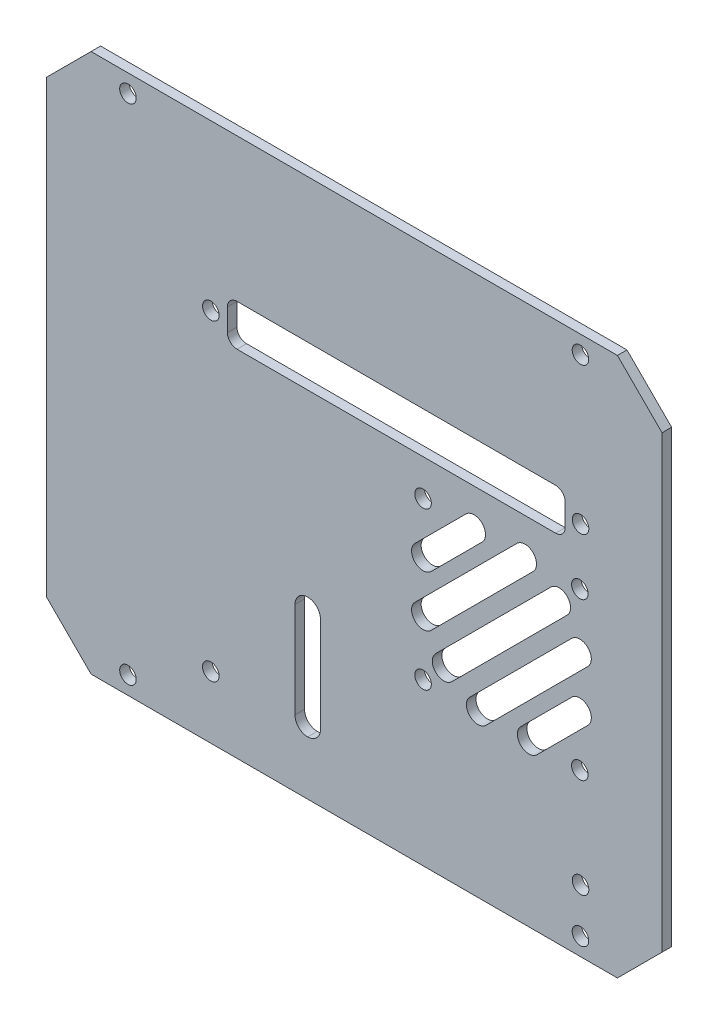
SolidWorks part; units mm, degrees
ref_plane "前视基准面" through (0, 0, 0) normal (0, 0, 1) x (1, 0, 0)
ref_plane "上视基准面" through (0, 0, 0) normal (0, 1, 0) x (1, 0, 0)
ref_plane "右视基准面" through (0, 0, 0) normal (1, 0, 0) x (0, 0, -1)
sketch "草图2" plane through (0, 0, -39.19) normal (0, 0, -1) x (-1, 0, 0)
  line L32 (-47.3467, -34.0538) -> (-40.3426, -41.058)
  line L33 (-40.3426, -41.058) -> (42.2491, -41.058)
  line L34 (42.2491, -41.058) -> (49.2533, -34.0538)
  line L35 (49.2533, -34.0538) -> (49.2533, 36.5378)
  line L36 (49.2533, 36.5378) -> (42.2491, 43.542)
  line L37 (-47.3467, 36.5378) -> (-47.3467, -34.0538)
  line L38 (-40.3426, 43.542) -> (-47.3467, 36.5378)
  line L39 (42.2491, 43.542) -> (-40.3426, 43.542)
  line L40 (-47.3467, -34.0538) -> (-40.3426, -41.058)
  line L41 (-40.3426, -41.058) -> (42.2491, -41.058)
  line L42 (42.2491, -41.058) -> (49.2533, -34.0538)
  line L43 (49.2533, -34.0538) -> (49.2533, 36.5378)
  line L44 (49.2533, 36.5378) -> (42.2491, 43.542)
  line L45 (-47.3467, 36.5378) -> (-47.3467, -34.0538)
  line L46 (-40.3426, 43.542) -> (-47.3467, 36.5378)
  line L47 (42.2491, 43.542) -> (-40.3426, 43.542)
  dimension "D1" = 0.2
extrude "凸台-拉伸1" add sketch "草图2" along normal blind 1.5
sketch "草图3" plane through (0, 0, -40.69) normal (0, 0, -1) x (-1, 0, 0)
  circle A0 centre (-34.5467, -38.258) radius 1.3
  circle A1 centre (36.4533, -38.258) radius 1.3
  circle A2 centre (-34.5467, 40.742) radius 1.3
  circle A3 centre (36.4533, 40.742) radius 1.3
  dimension "D1" = 2.6
extrude "切除-拉伸1" cut sketch "草图3" against normal through all
sketch "草图4" plane through (0, 0, -40.69) normal (0, 0, -1) x (-1, 0, 0)
  circle A1 centre (23.4533, -31.2932) radius 1.3
  circle A2 centre (23.4533, -31.2932) radius 1.3
  circle A3 centre (-34.5583, -31.2932) radius 1.3
  circle A4 centre (-34.5583, -31.2932) radius 1.3
  circle A5 centre (23.4533, 17.742) radius 1.3
  circle A6 centre (23.4533, 17.742) radius 1.3
  circle A7 centre (-34.5583, 17.742) radius 1.3
  circle A8 centre (-34.5583, 17.742) radius 1.3
  dimension "D1" = 0
  dimension "D2" = 0
  dimension "D3" = 0
  dimension "D4" = 0
extrude "切除-拉伸2" cut sketch "草图4" against normal up to next
sketch "草图5" plane through (0, 0, -40.69) normal (0, 0, -1) x (-1, 0, 0)
  line L0 (-40.4254, -41.258) -> (42.3319, -41.258) construction
  line L1 (-32.1467, 14.542) -> (20.8533, 14.542)
  line L2 (-32.1467, 14.542) -> (-32.1467, 21.042)
  line L3 (-32.1467, 21.042) -> (20.8533, 21.042)
  line L4 (20.8533, 14.542) -> (20.8533, 21.042)
  line L7 (-47.3467, 36.5378) -> (-47.3467, -34.0538) construction
  dimension "D1" = 53
  dimension "D2" = 6.5
  dimension "D3" = 15.2
  dimension "D4" = 55.8
extrude "切除-拉伸3" cut sketch "草图5" against normal up to next
fillet "圆角1" radius 1.5 4 edges at (32.1467, 21.042, -39.94) (32.1467, 14.542, -39.94) (-20.8533, 14.542, -39.94) (-20.8533, 21.042, -39.94)
sketch "草图7" plane through (0, 0, -40.69) normal (0, 0, -1) x (-1, 0, 0)
  circle A0 centre (-34.4467, 8.842) radius 1.3
  circle A1 centre (-34.4467, -15.758) radius 1.3
  circle A2 centre (-9.8467, 8.842) radius 1.3
  circle A3 centre (-9.8467, -15.758) radius 1.3
  circle A4 centre (-34.5583, 17.742) radius 1.3 construction
extrude "切除-拉伸4" cut sketch "草图7" against normal up to next
sketch "草图8" plane through (0, 0, -40.69) normal (0, 0, -1) x (-1, 0, 0)
  line L0 (-34.4467, 8.842) -> (-9.8467, -15.758) construction
  line L1 (-34.4467, 8.842) -> (-9.8467, 8.842) construction
  line L2 (-34.4467, 8.842) -> (-34.4467, -15.758) construction
  line L3 (-34.4467, -15.758) -> (-9.8467, -15.758) construction
  line L4 (-9.8467, 8.842) -> (-9.8467, -15.758) construction
  line L5 (-31.194, 5.5893) -> (-13.0994, -12.5053) construction
  line L6 (-29.9212, 6.8621) -> (-11.8266, -11.2325)
  line L7 (-32.4668, 4.3165) -> (-14.3722, -13.7781)
  line L8 (-34.4467, 0.242) -> (-18.4467, -15.758) construction
  line L9 (-33.1739, 1.5148) -> (-17.1739, -14.4852)
  line L10 (-35.7195, -1.0308) -> (-19.7195, -17.0308)
  line L11 (-25.8467, 8.842) -> (-9.8467, -7.158) construction
  line L12 (-24.5739, 10.1148) -> (-8.5739, -5.8852)
  line L13 (-27.1195, 7.5692) -> (-11.1195, -8.4308)
  line L14 (-17.8467, 8.842) -> (-9.8467, 0.842) construction
  line L15 (-16.5739, 10.1148) -> (-8.5739, 2.1148)
  line L16 (-19.1195, 7.5692) -> (-11.1195, -0.4308)
  line L17 (-34.4467, -7.758) -> (-26.4467, -15.758) construction
  line L18 (-33.1739, -6.4852) -> (-25.1739, -14.4852)
  line L19 (-35.7195, -9.0308) -> (-27.7195, -17.0308)
  arc A1 (-29.9212, 6.8621) -> (-32.4668, 4.3165) centre (-31.194, 5.5893) ccw
  arc A2 (-14.3722, -13.7781) -> (-11.8266, -11.2325) centre (-13.0994, -12.5053) ccw
  arc A3 (-33.1739, 1.5148) -> (-35.7195, -1.0308) centre (-34.4467, 0.242) ccw
  arc A4 (-19.7195, -17.0308) -> (-17.1739, -14.4852) centre (-18.4467, -15.758) ccw
  arc A5 (-24.5739, 10.1148) -> (-27.1195, 7.5692) centre (-25.8467, 8.842) ccw
  arc A6 (-11.1195, -8.4308) -> (-8.5739, -5.8852) centre (-9.8467, -7.158) ccw
  arc A7 (-16.5739, 10.1148) -> (-19.1195, 7.5692) centre (-17.8467, 8.842) ccw
  arc A8 (-11.1195, -0.4308) -> (-8.5739, 2.1148) centre (-9.8467, 0.842) ccw
  arc A9 (-33.1739, -6.4852) -> (-35.7195, -9.0308) centre (-34.4467, -7.758) ccw
  arc A10 (-27.7195, -17.0308) -> (-25.1739, -14.4852) centre (-26.4467, -15.758) ccw
  point P10 (-22.1467, -3.458)
  point P15 (-26.4467, -7.758)
  point P22 (-17.8467, 0.842)
  point P29 (-13.8467, 4.842)
  point P36 (-30.4467, -11.758)
  dimension "D1" = 1.8
  dimension "D2" = 1.8
  dimension "D3" = 1.8
  dimension "D4" = 1.8
  dimension "D5" = 1.8
  dimension "D6" = 8
  dimension "D7" = 8
  dimension "D8" = 8
  dimension "D9" = 8
  dimension "D10" = 4.6
  dimension "D11" = 4.6
extrude "切除-拉伸5" cut sketch "草图8" against normal up to next
sketch "草图9" plane through (0, 0, -40.69) normal (0, 0, -1) x (-1, 0, 0)
  line L0 (49.2533, -34.0538) -> (49.2533, 36.5378) construction
  line L1 (6.2533, -13.5932) -> (10.2533, -13.5932)
  line L2 (6.2533, -13.5932) -> (6.2533, -32.5932)
  line L3 (6.2533, -32.5932) -> (10.2533, -32.5932)
  line L4 (10.2533, -13.5932) -> (10.2533, -32.5932)
  circle A1 centre (23.4533, -31.2932) radius 1.3 construction
  dimension "D1" = 39
  dimension "D2" = 4
  dimension "D3" = 19
extrude "切除-拉伸6" cut sketch "草图9" against normal blind 8
fillet "圆角2" radius 2 4 edges at (-6.2533, -32.5932, -39.94) (-10.2533, -32.5932, -39.94) (-10.2533, -13.5932, -39.94) (-6.2533, -13.5932, -39.94)
